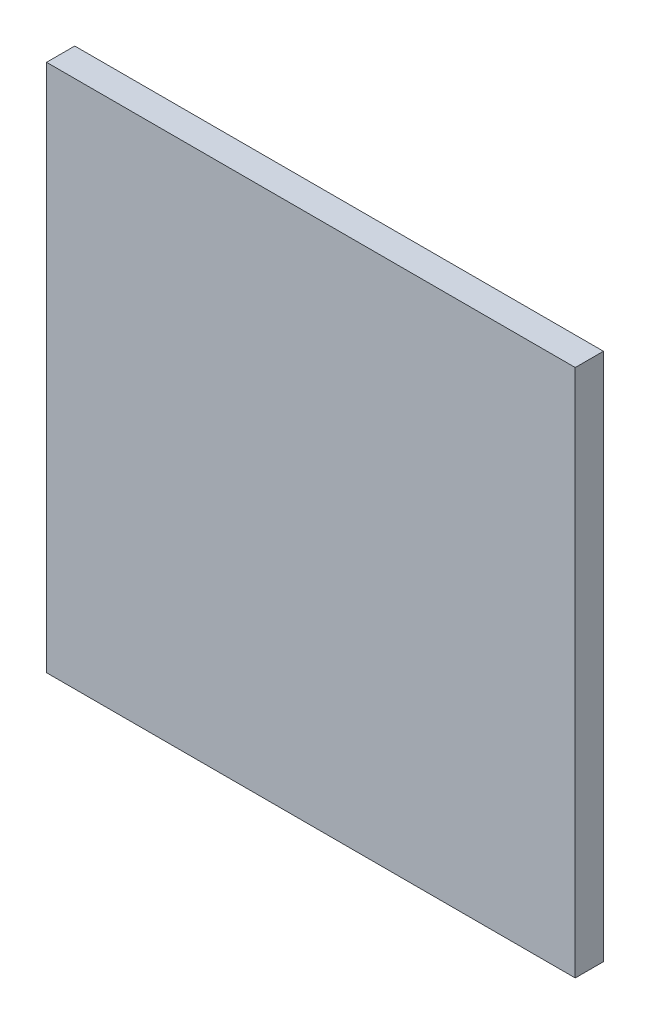
SolidWorks part; units mm, degrees
note: The reader was unsure of these and kept them because the rebuilt part matched: thickness of "Базовая кромка1", "Листовой металл1".
material "Простая углеродистая сталь"
ref_plane "Спереди" through (0, 0, 0) normal (0, 0, 1) x (1, 0, 0)
ref_plane "Сверху" through (0, 0, 0) normal (0, 1, 0) x (1, 0, 0)
ref_plane "Справа" through (0, 0, 0) normal (1, 0, 0) x (0, 0, -1)
sketch "Эскиз1" plane through (0, 0, 0) normal (0, 0, 1) x (1, 0, 0)
  line L1 (0, 0) -> (300, 0)
  line L2 (0, 0) -> (0, -300)
  line L3 (0, -300) -> (300, -300)
  line L4 (300, 0) -> (300, -300)
  dimension "D1" = 300
  dimension "D2" = 300
base flange "Базовая кромка1" sketch "Эскиз1" thickness 16 reverse thickness direction no parameters "D1"=3
sketch "Сгиб-Линии1" [suppressed] plane through (0, 0, 0) normal (0, 1, 0) x (1, 0, 0)
sketch "Граничная рамка1" [suppressed] plane through (0, 0, 0) normal (0, 1, 0) x (1, 0, 0)
sheet metal parameters "Листовой металл1" thickness 16 parameters "D1"=3, "D7"=20
flat pattern "Развертка1" [suppressed]
sketch "Сгиб-Линии2" plane through (0, 0, 0) normal (0, 1, 0) x (1, 0, 0)
sketch3d "Граничная рамка2" [suppressed]
  line L0 (0, -300, 0) -> (300, -300, 0) construction
  line L1 (0, 0, 0) -> (300, 0, 0) construction
  line L2 (0, -300, 0) -> (0, 0, 0) construction
  line L3 (300, -300, 0) -> (300, 0, 0) construction
